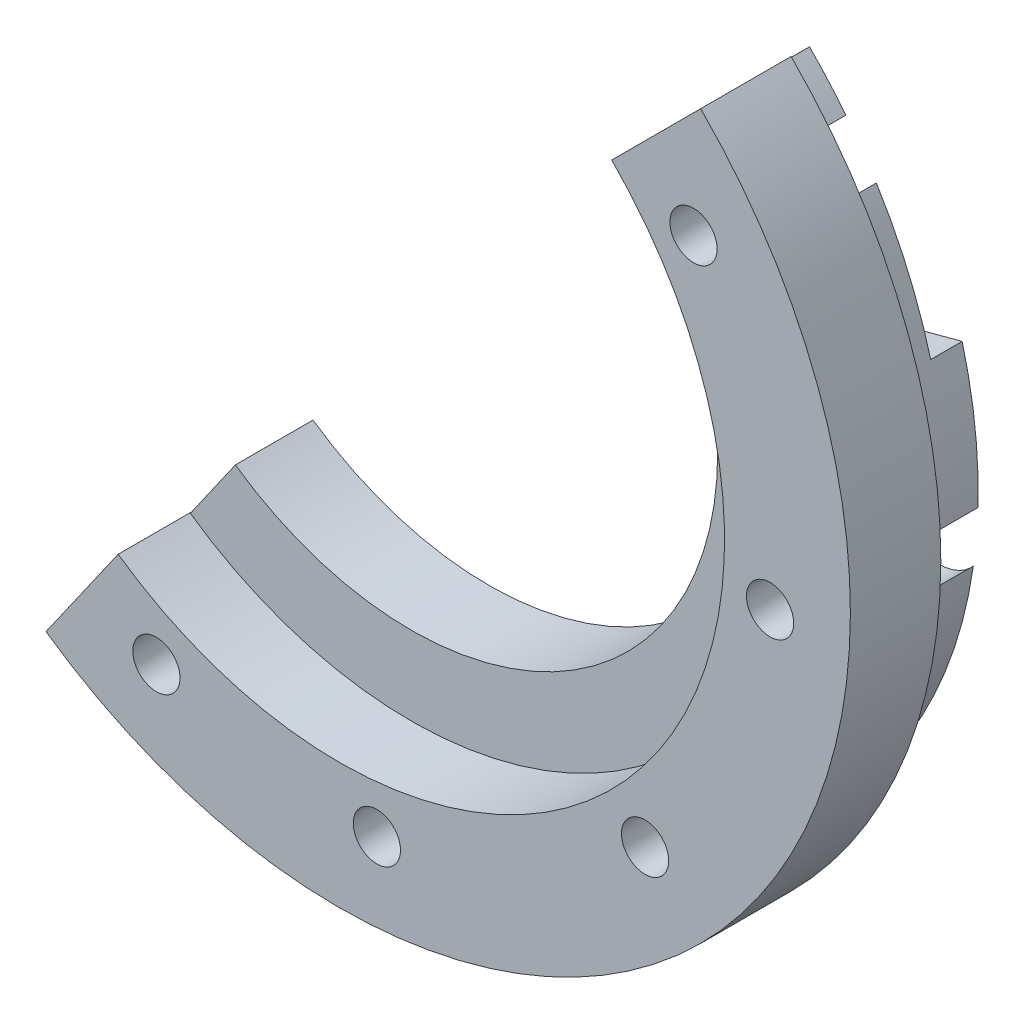
SolidWorks part; units mm, degrees
ref_plane "Front Plane" through (0, 0, 0) normal (0, 0, 1) x (1, 0, 0)
ref_plane "Top Plane" through (0, 0, 0) normal (0, 1, 0) x (1, 0, 0)
ref_plane "Right Plane" through (0, 0, 0) normal (1, 0, 0) x (0, 0, -1)
ref_plane "PZ_p24_600" through (0, 0, 24.6) normal (0, 0, 1) x (1, 0, 0)
sketch "S_prism1" plane through (0, 0, 24.6) normal (0, 0, 1) x (1, 0, 0)
  line L0 (-14.913, -21.298) -> (-11.2421, -16.0554)
  line L1 (13.8593, 13.8593) -> (18.3848, 18.3848)
  arc A0 (18.3848, 18.3848) -> (-14.913, -21.298) centre (0, 0) cw
  arc A1 (-11.2421, -16.0554) -> (13.8593, 13.8593) centre (0, 0) ccw
extrude "Boss_1" add sketch "S_prism1" along normal blind 5.6
ref_plane "PZ_p21_600" through (0, 0, 21.6) normal (0, 0, 1) x (1, 0, 0)
sketch "S_prism2" plane through (0, 0, 21.6) normal (0, 0, 1) x (1, 0, 0)
  line L0 (-13.6845, -19.5945) -> (-8.9322, -12.7897)
  line L1 (11.0443, 11.0174) -> (16.9205, 16.8792)
  arc A0 (16.9205, 16.8792) -> (-13.6845, -19.5945) centre (0, 0) cw
  arc A1 (-8.9322, -12.7897) -> (11.0443, 11.0174) centre (0, 0) ccw
extrude "Boss_2" add sketch "S_prism2" along normal blind 4.95
ref_plane "PZ_p24_500" through (0, 0, 24.5) normal (0, 0, 1) x (1, 0, 0)
sketch "S_pcut3" plane through (0, 0, 24.5) normal (0, 0, 1) x (1, 0, 0)
  line L0 (-15.4, -21.1962) -> (-14.0481, -19.3355)
  line L1 (16.6023, 17.1922) -> (18.2, 18.8467)
  arc A0 (18.2, 18.8467) -> (-15.4, -21.1962) centre (0, 0) cw
  arc A1 (-14.0481, -19.3355) -> (16.6023, 17.1922) centre (0, 0) ccw
extrude "Cut_3" cut sketch "S_pcut3" along normal blind 1.1
ref_plane "PZ_p21_500" through (0, 0, 21.5) normal (0, 0, 1) x (1, 0, 0)
sketch "S_pcut4" plane through (0, 0, 21.5) normal (0, 0, 1) x (1, 0, 0)
  line L0 (-9.9923, -13.7533) -> (-9.1107, -12.5398)
  line L1 (10.7672, 11.1498) -> (11.8092, 12.2288)
  arc A0 (11.8092, 12.2288) -> (-9.9923, -13.7533) centre (0, 0) cw
  arc A1 (-9.1107, -12.5398) -> (10.7672, 11.1498) centre (0, 0) ccw
extrude "Cut_4" cut sketch "S_pcut4" along normal blind 1.1
sketch "S_pcut5" plane through (0, 0, 21.5) normal (0, 0, 1) x (1, 0, 0)
  line L0 (-10.6977, -14.7241) -> (-9.1107, -12.5398)
  line L1 (7.75, -13.4234) -> (9.1, -15.7617)
  arc A0 (9.1, -15.7617) -> (-10.6977, -14.7241) centre (0, 0) cw
  arc A1 (-9.1107, -12.5398) -> (7.75, -13.4234) centre (0, 0) ccw
extrude "Cut_5" cut sketch "S_pcut5" along normal blind 1.1
sketch "S_pcut6" plane through (0, 0, 21.5) normal (0, 0, 1) x (1, 0, 0)
  line L0 (18.5458, 4.9693) -> (14.9719, 4.0117)
  line L1 (10.7672, 11.1498) -> (13.3374, 13.8113)
  arc A0 (13.3374, 13.8113) -> (18.5458, 4.9693) centre (0, 0) cw
  arc A1 (14.9719, 4.0117) -> (10.7672, 11.1498) centre (0, 0) ccw
extrude "Cut_6" cut sketch "S_pcut6" along normal blind 1.1
sketch "S_pcut7" plane through (0, 0, 21.5) normal (0, 0, 1) x (1, 0, 0)
  line L0 (25.3073, 6.7811) -> (19.6083, 5.254)
  line L1 (14.1016, 14.6026) -> (18.2, 18.8467)
  arc A0 (18.2, 18.8467) -> (25.3073, 6.7811) centre (0, 0) cw
  arc A1 (19.6083, 5.254) -> (14.1016, 14.6026) centre (0, 0) ccw
extrude "Cut_7" cut sketch "S_pcut7" along normal blind 1.7
sketch "S_pcut8" plane through (0, 0, 21.5) normal (0, 0, 1) x (1, 0, 0)
  line L0 (-15.4, -21.1962) -> (-11.932, -16.423)
  line L1 (10.15, -17.5803) -> (13.1, -22.6899)
  arc A0 (13.1, -22.6899) -> (-15.4, -21.1962) centre (0, 0) cw
  arc A1 (-11.932, -16.423) -> (10.15, -17.5803) centre (0, 0) ccw
extrude "Cut_8" cut sketch "S_pcut8" along normal blind 1.7
sketch "S_pcut9" plane through (0, 0, 21.5) normal (0, 0, 1) x (1, 0, 0)
  line L0 (-15.4, -21.1962) -> (-11.932, -16.423)
  line L1 (-5.254, -19.6083) -> (-6.7811, -25.3073)
  arc A0 (-6.7811, -25.3073) -> (-15.4, -21.1962) centre (0, 0) cw
  arc A1 (-11.932, -16.423) -> (-5.254, -19.6083) centre (0, 0) ccw
extrude "Cut_9" cut sketch "S_pcut9" along normal blind 1.9
sketch "S_pcut10" plane through (0, 0, 21.5) normal (0, 0, 1) x (1, 0, 0)
  line L0 (-15.4, -21.1962) -> (-12.5198, -17.2321)
  line L1 (-7.9791, -19.749) -> (-9.8147, -24.2922)
  arc A0 (-9.8147, -24.2922) -> (-15.4, -21.1962) centre (0, 0) cw
  arc A1 (-12.5198, -17.2321) -> (-7.9791, -19.749) centre (0, 0) ccw
extrude "Cut_10" cut sketch "S_pcut10" along normal blind 2.9
sketch "S_hole11" plane through (0, 0, 21.5) normal (0, 0, 1) x (1, 0, 0)
  circle A0 centre (18.0213, 12.6187) radius 1.2
  dimension "D1_S_hole11" = 2.4
  dimension "P2" = 18.0213
  dimension "P3" = 12.6187
extrude "Hole_11" cut sketch "S_hole11" along normal blind 8.8
sketch "S_hole12" plane through (0, 0, 21.5) normal (0, 0, 1) x (1, 0, 0)
  circle A0 centre (18.0213, 12.6187) radius 2.3
  dimension "D1_S_hole12" = 4.6
  dimension "P2" = 18.0213
  dimension "P3" = 12.6187
extrude "Hole_12" cut sketch "S_hole12" along normal blind 3.1
sketch "S_hole13" plane through (0, 0, 21.5) normal (0, 0, 1) x (1, 0, 0)
  circle A0 centre (21.9163, -1.9174) radius 1.2
  dimension "D1_S_hole13" = 2.4
  dimension "P2" = 21.9163
  dimension "P3" = 1.9174
extrude "Hole_13" cut sketch "S_hole13" along normal blind 8.8
sketch "S_hole14" plane through (0, 0, 21.5) normal (0, 0, 1) x (1, 0, 0)
  circle A0 centre (21.9163, -1.9174) radius 2.3
  dimension "D1_S_hole14" = 4.6
  dimension "P2" = 21.9163
  dimension "P3" = 1.9174
extrude "Hole_14" cut sketch "S_hole14" along normal blind 3.1
sketch "S_hole15" plane through (0, 0, 21.5) normal (0, 0, 1) x (1, 0, 0)
  circle A0 centre (15.5563, -15.5563) radius 1.2
  dimension "D1_S_hole15" = 2.4
  dimension "P2" = 15.5563
  dimension "P3" = 15.5563
extrude "Hole_15" cut sketch "S_hole15" along normal blind 8.8
sketch "S_hole16" plane through (0, 0, 21.5) normal (0, 0, 1) x (1, 0, 0)
  circle A0 centre (15.5563, -15.5563) radius 2.3
  dimension "D1_S_hole16" = 4.6
  dimension "P2" = 15.5563
  dimension "P3" = 15.5563
extrude "Hole_16" cut sketch "S_hole16" along normal blind 3.1
sketch "S_hole17" plane through (0, 0, 21.5) normal (0, 0, 1) x (1, 0, 0)
  circle A0 centre (1.9174, -21.9163) radius 1.2
  dimension "D1_S_hole17" = 2.4
  dimension "P2" = 1.9174
  dimension "P3" = 21.9163
extrude "Hole_17" cut sketch "S_hole17" along normal blind 8.8
sketch "S_hole18" plane through (0, 0, 21.5) normal (0, 0, 1) x (1, 0, 0)
  circle A0 centre (1.9174, -21.9163) radius 2.3
  dimension "D1_S_hole18" = 4.6
  dimension "P2" = 1.9174
  dimension "P3" = 21.9163
extrude "Hole_18" cut sketch "S_hole18" along normal blind 3.1
sketch "S_hole19" plane through (0, 0, 21.5) normal (0, 0, 1) x (1, 0, 0)
  circle A0 centre (-9.2976, -19.9388) radius 1.2
  dimension "D1_S_hole19" = 2.4
  dimension "P2" = 9.2976
  dimension "P3" = 19.9388
extrude "Hole_19" cut sketch "S_hole19" along normal blind 8.8
sketch "S_hole20" plane through (0, 0, 21.5) normal (0, 0, 1) x (1, 0, 0)
  circle A0 centre (-9.2976, -19.9388) radius 2.3
  dimension "D1_S_hole20" = 4.6
  dimension "P2" = 9.2976
  dimension "P3" = 19.9388
extrude "Hole_20" cut sketch "S_hole20" along normal blind 3.1
equation "\"plate_t\" = 3"
equation "\"clearance\" = 0.5"
